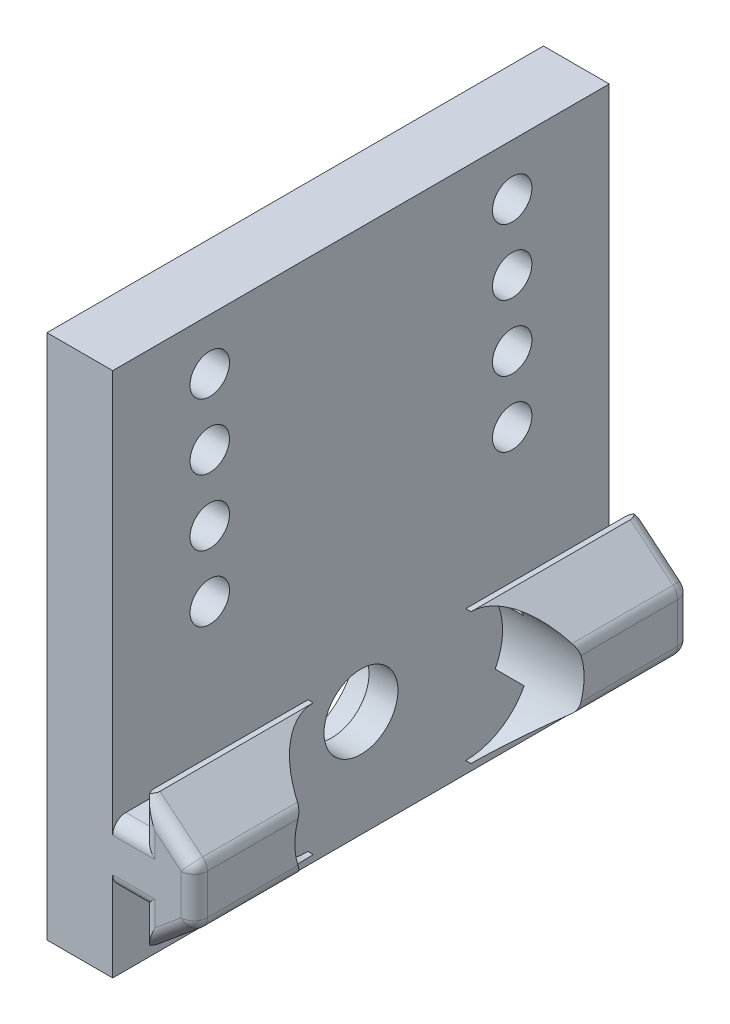
SolidWorks part; units mm, degrees
ref_plane "Front Plane" through (0, 0, 0) normal (0, 0, 1) x (1, 0, 0)
ref_plane "Top Plane" through (0, 0, 0) normal (0, 1, 0) x (1, 0, 0)
ref_plane "Right Plane" through (0, 0, 0) normal (1, 0, 0) x (0, 0, -1)
ref_plane "Plane1" through (0, 0, 23.6855) normal (0, 0, 1) x (1, 0, 0)
sketch "Sketch1" plane through (0, 0, 23.6855) normal (0, 0, 1) x (1, 0, 0)
  line L0 (3.302, 6.35) -> (-4.064, 6.35)
  line L1 (-4.064, 6.35) -> (-4.064, -6.35)
  line L2 (-4.064, -6.35) -> (3.302, -6.35)
  line L3 (3.302, -6.35) -> (7.874, -2.54)
  line L4 (7.874, -2.54) -> (7.874, 2.54)
  line L5 (7.874, 2.54) -> (3.302, 6.35)
extrude "Boss-Extrude1" add sketch "Sketch1" against normal blind 47.9552
sketch "Sketch2" plane through (0, 0, 23.6855) normal (0, 0, 1) x (1, 0, 0)
  line L0 (-4.064, 6.35) -> (-4.064, 2.921)
  line L1 (-4.064, 2.921) -> (2.794, 2.921)
  line L2 (2.794, 2.921) -> (2.794, 6.35)
  line L3 (2.794, 6.35) -> (-4.064, 6.35)
extrude "Cut-Extrude1" cut sketch "Sketch2" against normal through all
sketch "Sketch3" plane through (0, 2.921, 0) normal (0, 1, 0) x (-1, 0, 0)
  line L0 (4.064, -24.2697) -> (0, -24.2697)
  line L1 (0, -24.2697) -> (0, 23.6855)
  line L2 (0, 23.6855) -> (4.064, 23.6855)
  line L3 (4.064, 23.6855) -> (4.064, -24.2697)
  line L4 (55, 23.6855) -> (-55, 23.6855) construction
  dimension "D1" = 47.9552
extrude "Boss-Extrude2" add sketch "Sketch3" along normal blind 7.366
sketch "Sketch4" plane through (0, 0, 23.6855) normal (0, 0, 1) x (1, 0, 0)
  line L0 (-4.064, -6.35) -> (2.794, -6.35)
  line L1 (2.794, -6.35) -> (2.794, -2.921)
  line L2 (2.794, -2.921) -> (-4.064, -2.921)
  line L3 (-4.064, -2.921) -> (-4.064, -6.35)
extrude "Cut-Extrude2" cut sketch "Sketch4" against normal through all
sketch "Sketch5" plane through (0, -2.921, 0) normal (0, -1, 0) x (1, 0, 0)
  line L0 (0, -24.2697) -> (-4.064, -24.2697)
  line L1 (-4.064, -24.2697) -> (-4.064, 23.6855)
  line L2 (-4.064, 23.6855) -> (0, 23.6855)
  line L3 (0, 23.6855) -> (0, -24.2697)
  point P4 (0, 0)
  dimension "D1" = 4.064
  dimension "D2" = 47.9552
extrude "Boss-Extrude3" add sketch "Sketch5" along normal blind 7.366
hole_wizard "#3 Clearance Hole1" [suppressed] positions "Sketch7" profile "Sketch6" hole size "#3" standard "ANSI Inch"
sketch "Sketch7" plane through (-4.064, 0, 0) normal (-1, 0, 0) x (0, 0, 1)
  point P0 (12.7, 0)
  point P1 (-12.7, 0)
sketch "Sketch6" plane through (-4.064, 0, 12.7) normal (0, 1, 0) x (0, 0, 1)
  line L0 (0, 0) -> (0, 11.938)
  line L1 (0, 11.938) -> (1.3843, 11.938)
  line L2 (1.3843, 11.938) -> (1.3843, 0)
  line L5 (1.3843, 0) -> (0, 0)
  line L11 (0, -6.35) -> (0, 107.95) construction
  dimension "Thru Hole Dia." = 2.7686
  dimension "Thru Hole Depth" = 11.938
sketch "Sketch12" [suppressed] plane through (7.874, 0, 0) normal (1, 0, 0) x (0, 0, -1)
  line L0 (-12.7, 1.3843) -> (-12.7, -1.3843) construction
  line L1 (12.7, 1.3843) -> (12.7, -1.3843) construction
  circle A0 centre (-12.7, 0) radius 1.3843 construction
  circle A1 centre (12.7, 0) radius 1.3843 construction
  point P5 (-12.7, 0)
  point P11 (12.7, 0)
hole_wizard "CBORE for #10 Button Head Cap Screw1" [suppressed] positions "Sketch13" profile "Sketch14" counterbore size "#10" standard "ANSI Inch"
sketch "Sketch13" [suppressed] plane through (7.874, 0, 0) normal (1, 0, 0) x (0, 0, -1)
  point P0 (-12.7, 0)
  point P3 (12.7, 0)
sketch "Sketch14" plane through (7.874, 0, 12.7) normal (0, 1, 0) x (0, 0, -1)
  line L0 (0, 0) -> (0, 11.938)
  line L1 (0, 11.938) -> (2.5527, 11.938)
  line L3 (2.5527, 11.938) -> (2.5527, 3.2004)
  line L4 (2.5527, 3.2004) -> (4.9606, 3.2004)
  line L5 (4.9606, 3.2004) -> (4.9606, 0)
  line L7 (4.9606, 0) -> (0, 0)
  line L11 (0, -6.35) -> (0, 107.95) construction
  dimension "Thru Hole Dia." = 5.1054
  dimension "Thru Hole Depth" = 11.938
  dimension "C'Bore Dia." = 9.9212
  dimension "C'Bore Depth" = 3.2004
fillet "Fillet1" radius 1.27 2 edges at (7.874, -2.54, -0.2921) (7.874, 2.54, -0.2921)
fillet "Fillet3" radius 1.27 9 edges at (5.3595, -4.6354, -24.2697) (7.7541, -2.4838, -24.2697) (5.3595, 4.6354, -24.2697) (7.7541, 2.4838, -24.2697) (1.397, -2.921, -24.2697) (1.397, 2.921, -24.2697) (2.794, 4.6355, -24.2697) (2.794, -4.6355, -24.2697) (7.874, 0, -24.2697)
fillet "Fillet5" radius 1.27 9 edges at (5.3595, -4.6354, 23.6855) (7.7541, -2.4838, 23.6855) (5.3595, 4.6354, 23.6855) (7.7541, 2.4838, 23.6855) (2.794, 4.6355, 23.6855) (1.397, 2.921, 23.6855) (1.397, -2.921, 23.6855) (2.794, -4.6355, 23.6855) (7.874, 0, 23.6855)
sketch "Sketch15" plane through (-4.064, 0, 0) normal (-1, 0, 0) x (0, 0, 1)
  line L1 (-24.2697, 10.287) -> (23.6855, 10.287)
  line L2 (-24.2697, 10.287) -> (-24.2697, -10.287)
  line L3 (-24.2697, -10.287) -> (23.6855, -10.287)
  line L4 (23.6855, 10.287) -> (23.6855, -10.287)
extrude "Cut-Extrude3" cut sketch "Sketch15" against normal blind 1.905
sketch "Sketch17" plane through (0, 0, 0) normal (1, 0, 0) x (0, 0, -1)
  line L0 (-23.6855, 55) -> (-23.6855, -55) construction
  line L1 (24.2697, 10.287) -> (-23.6855, 10.287)
  line L2 (24.2697, 10.287) -> (24.2697, 40.513)
  line L3 (24.2697, 40.513) -> (-23.6855, 40.513)
  line L4 (-23.6855, 10.287) -> (-23.6855, 40.513)
  line L5 (24.2697, -10.287) -> (-23.6855, -10.287) construction
  line L6 (-23.6855, 12.7) -> (24.2697, 12.7) construction
  dimension "D1" = 50.8
  dimension "D2" = 47.9552
  dimension "D3" = 12.7
extrude "Boss-Extrude4" add sketch "Sketch17" against normal blind 6.35
sketch "Sketch20" plane through (-2.159, 0, 0) normal (-1, 0, 0) x (0, 0, 1)
  line L0 (23.6855, -55) -> (23.6855, 55) construction
  line L1 (-24.2697, 10.287) -> (23.6855, 10.287)
  line L2 (-24.2697, 10.287) -> (-24.2697, -10.287)
  line L3 (-24.2697, -10.287) -> (23.6855, -10.287)
  line L4 (23.6855, 10.287) -> (23.6855, -10.287)
  line L5 (-24.2697, -10.287) -> (23.6855, -10.287) construction
extrude "Boss-Extrude6" add sketch "Sketch20" along normal up to surface (4.191 mm away) up to face at (-6.35, 25.4, -0.2921)
sketch "Sketch21" plane through (-6.35, 0, 0) normal (-1, 0, 0) x (0, 0, 1)
  line L0 (-24.2697, 12.7) -> (23.6855, 12.7) construction
  line L1 (-24.2697, -10.287) -> (-24.2697, 40.513) construction
  line L2 (23.6855, 40.513) -> (23.6855, -10.287) construction
  line L3 (-24.2697, 1.9452) -> (-24.2697, -1.9452) construction
  circle A0 centre (-14.8971, 16.51) radius 1.905
  circle A1 centre (14.3129, 16.51) radius 1.905
  circle A2 centre (14.3129, 22.86) radius 1.905
  circle A3 centre (14.3129, 29.21) radius 1.905
  circle A4 centre (14.3129, 35.56) radius 1.905
  circle A5 centre (-14.8971, 22.86) radius 1.905
  circle A6 centre (-14.8971, 29.21) radius 1.905
  circle A7 centre (-14.8971, 35.56) radius 1.905
  point P10 (-24.2697, 0)
  point P12 (-14.5364, 16.6249)
  point P13 (0, 0)
  dimension "D1" = 3.81
  dimension "D2" = 12.7
  dimension "D5" = 9.3726
  dimension "D6" = 3.81
  dimension "D3" = 2
  dimension "D4" = 4
extrude "Cut-Extrude4" cut sketch "Sketch21" against normal through all
sketch "Sketch22" plane through (0, 0, 0) normal (1, 0, 0) x (0, 0, -1)
  line L0 (7.62, 0) -> (-7.62, 0) construction
  line L1 (7.62, -6.35) -> (-7.62, -6.35)
  line L2 (7.62, 6.35) -> (-7.62, 6.35)
  arc A0 (7.62, -6.35) -> (7.62, 6.35) centre (7.62, 0) ccw
  arc A1 (-7.62, 6.35) -> (-7.62, -6.35) centre (-7.62, 0) ccw
  point P3 (0, 0)
  point P8 (0, 0)
  point P9 (-13.97, 0)
  point P11 (13.97, 0)
  dimension "D1" = 27.94
  dimension "D2" = 12.7
extrude "Cut-Extrude5" cut sketch "Sketch22" along normal through all
hole_wizard "CBORE for 1/4 Button Head Cap Screw1" positions "Sketch23" profile "Sketch24" counterbore size "1/4" standard "ANSI Inch" end condition up to next
sketch "Sketch23" plane through (-6.35, 0, 0) normal (-1, 0, 0) x (0, 0, 1)
  point P0 (-0.2921, 0)
sketch "Sketch24" plane through (-6.35, 0, -0.2921) normal (0, 1, 0) x (0, 0, 1)
  line L0 (0, 0) -> (0, 6.35)
  line L1 (0, 6.35) -> (3.5712, 6.35)
  line L3 (3.5712, 6.35) -> (3.5712, 3.556)
  line L4 (3.5712, 3.556) -> (5.9538, 3.556)
  line L5 (5.9538, 3.556) -> (5.9538, 0)
  line L7 (5.9538, 0) -> (0, 0)
  line L11 (0, -6.35) -> (0, 107.95) construction
  dimension "Thru Hole Dia." = 7.1425
  dimension "Thru Hole Depth" = 6.35
  dimension "C'Bore Dia." = 11.9075
  dimension "C'Bore Depth" = 3.556
